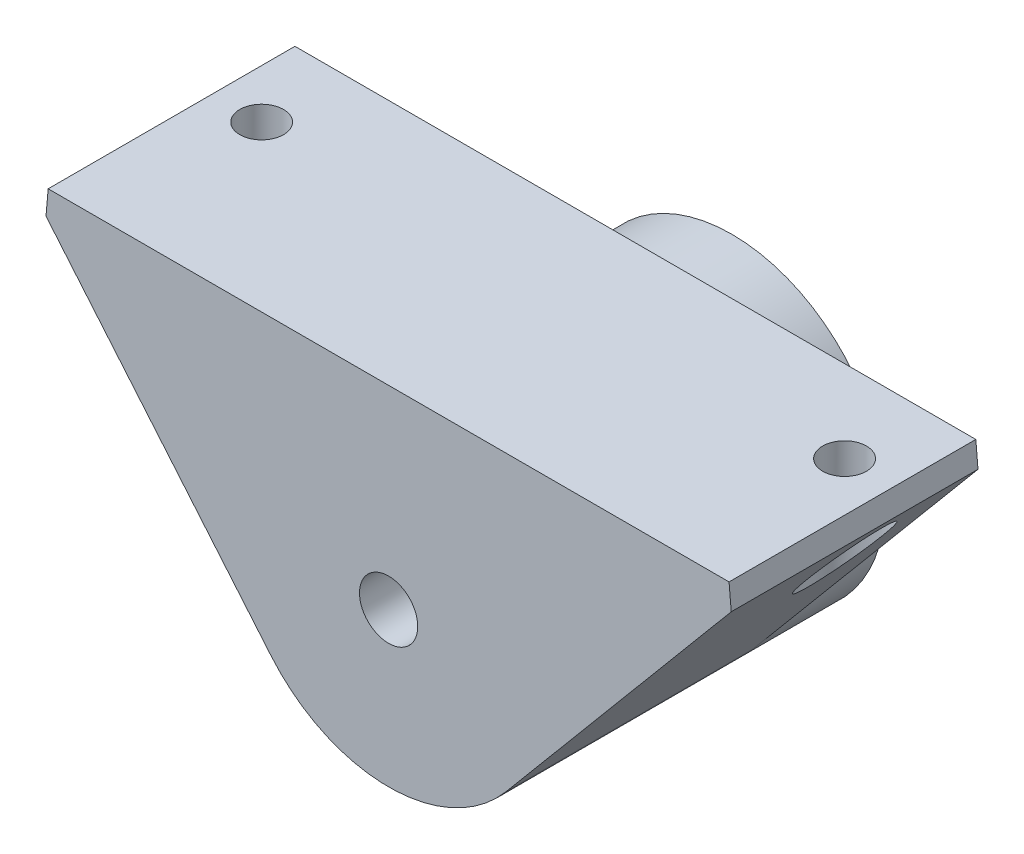
SolidWorks part; units mm, degrees
ref_plane "Front Plane" through (0, 0, 0) normal (0, 0, 1) x (1, 0, 0)
ref_plane "Top Plane" through (0, 0, 0) normal (0, 1, 0) x (1, 0, 0)
ref_plane "Right Plane" through (0, 0, 0) normal (1, 0, 0) x (0, 0, -1)
sketch "Sketch1" plane through (0, 0, 0) normal (0, 0, 1) x (1, 0, 0)
  circle A0 centre (0, 0) radius 15.5
  circle A1 centre (0, 0) radius 18.7
  circle A2 centre (0, 7.5) radius 6.5
  circle A3 centre (0, 0) radius 23.7
  dimension "D1" = 31
  dimension "D2" = 37.4
  dimension "D3" = 13
  dimension "D4" = 7.5
  dimension "D5" = 5
extrude "Boss-Extrude1" add sketch "Sketch1" against normal blind 48 contours A3 A1 region at (-23.0297, 0, 0)
extrude "Boss-Extrude2" add sketch "Sketch1<3>" along normal blind 5 contours A3 A1 | A1 A0 | A0 A2 | A2 region at (0, -1.6004, 0) region at (-18.1711, 0, 0) region at (0, 7.5, 0) region at (-23.0297, 0, 0)
sketch "Sketch1<3>" plane through (0, 0, 0) normal (0, 0, 1) x (1, 0, 0) same geometry as "Sketch1"
sketch "Sketch5" plane through (0, 0, 5) normal (0, 0, 1) x (1, 0, 0)
  line L0 (-56.1111, 30) -> (56.1111, 30)
  line L1 (-56.1111, 30) -> (-18.1553, -15.2341)
  line L2 (56.1111, 30) -> (18.1553, -15.2341)
  circle A0 centre (0, 0) radius 23.7 construction
  circle A1 centre (0, 0) radius 23.7
  circle M11 centre (0, 0) radius 23.7
  dimension "D1" = 30
  dimension "D2" = 50
extrude "Boss-Extrude3" add sketch "Sketch5" against normal blind 38.1 contours L2 L0 L1 M11 region at (0, 28.79, 5)
sketch "Sketch6" plane through (0, 30, 0) normal (0, 1, 0) x (1, 0, 0)
  line L0 (-45, 20.4) -> (45, 20.4) construction
  line L2 (-56.1111, -5) -> (56.1111, -5) construction
  point P3 (0, 20.4)
  dimension "D1" = 90
  dimension "D2" = 25.4
hole_wizard "1/4 Clearance Hole1" positions "Sketch7" profile "Sketch8" hole size "1/4" standard "ANSI Inch" end condition through all
sketch "Sketch7" plane through (0, 30, 0) normal (0, 1, 0) x (1, 0, 0)
  point P0 (-45, 20.4)
  point P3 (45, 20.4)
sketch "Sketch8" plane through (-45, 30, -20.4) normal (1, 0, 0) x (0, 0, 1)
  line L0 (0, 0) -> (0, 53.7)
  line L1 (0, 53.7) -> (3.3782, 53.7)
  line L2 (3.3782, 53.7) -> (3.3782, 0)
  line L5 (3.3782, 0) -> (0, 0)
  line L11 (0, -6.35) -> (0, 107.95) construction
  dimension "Thru Hole Dia." = 6.7564
  dimension "Thru Hole Depth" = 53.7
ref_plane "Plane2" through (0, 25, 0) normal (0, 1, 0) x (1, 0, 0)
sketch "Sketch9" plane through (0, 25, 0) normal (0, 1, 0) x (1, 0, 0)
  circle A0 centre (-45, 20.4) radius 5.715
  circle A1 centre (45, 20.4) radius 5.715
  dimension "D1" = 11.43
extrude "Cut-Extrude1" cut sketch "Sketch9" against normal through all
chamfer "Chamfer1" distance 5 angle 45 2 edges at (56.1111, 30, -14.05) (-56.1111, 30, -14.05) first distance on face at (50.715, 23.5691, -20.4) first distance on face at (-50.715, 23.5691, -20.4)
sketch "Sketch10" plane through (0, 0, 0) normal (0, 0, -1) x (-1, 0, 0)
  circle A0 centre (0, 0) radius 18.7 construction
  circle A1 centre (0, 0) radius 18.7
  circle A2 centre (0, 0) radius 4.5
  dimension "D1" = 9
extrude "Boss-Extrude4" add sketch "Sketch10" along normal up to surface (48 mm away) up to face at (18.7, 0, -48)
extrude "Cut-Extrude2" cut sketch "Sketch10<2>" against normal through all contours A2 region at (0, 0, 0)
sketch "Sketch10<2>" plane through (0, 0, 0) normal (0, 0, -1) x (-1, 0, 0) same geometry as "Sketch10"
